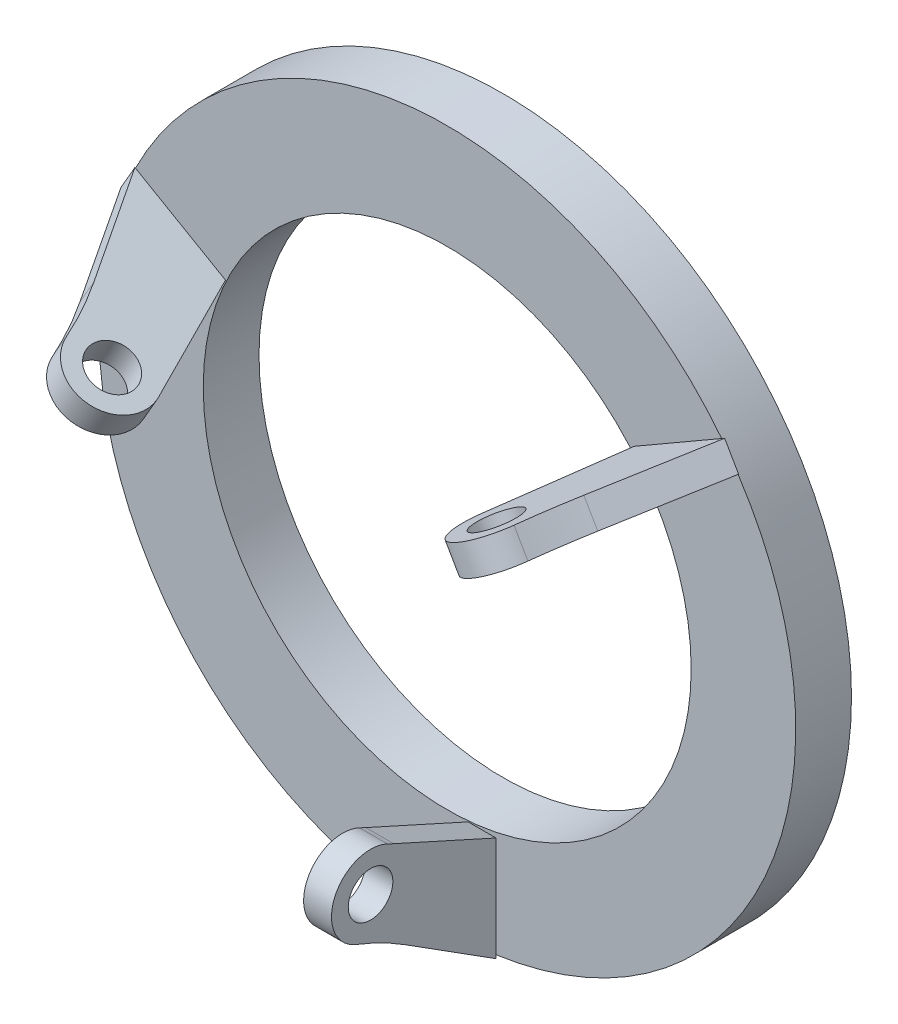
SolidWorks part; units mm, degrees
ref_plane "Piano frontale" through (0, 0, 0) normal (0, 0, 1) x (1, 0, 0)
ref_plane "Piano superiore" through (0, 0, 0) normal (0, 1, 0) x (1, 0, 0)
ref_plane "Piano destro" through (0, 0, 0) normal (1, 0, 0) x (0, 0, -1)
sketch "Schizzo1" plane through (0, 0, 0) normal (0, 0, 1) x (1, 0, 0)
  line L1 (-14.2894, 8.25) -> (-17.6966, 2.3486) construction
  line L2 (14.2894, 8.25) -> (9.3231, 16.8519) construction
  line L3 (12.8744, 5.701) -> (17.2045, 8.201) construction
  line L8 (20.1786, 13.0341) -> (11.4813, 8.0174) construction
  line L9 (11.4813, 8.0174) -> (9.5759, 11.3208) construction
  line L10 (9.5759, 11.3208) -> (18.2733, 16.3374) construction
  line L11 (18.2733, 16.3374) -> (20.1786, 13.0341) construction
  line L12 (-14.6251, 2.3486) -> (-23.5472, 7.5156) construction
  line L13 (-23.5472, 7.5156) -> (-21.5497, 10.9646) construction
  line L14 (-21.5497, 10.9646) -> (-12.6276, 5.7976) construction
  line L15 (-12.6276, 5.7976) -> (-14.6251, 2.3486) construction
  line L16 (12.1244, 7) -> (16.4545, 9.5) construction
  line L17 (0, -16.5) -> (10.6371, -16.5) construction
  line L18 (-1.5, -14) -> (-1.5, -19) construction
  line L19 (-11.3744, 8.299) -> (-15.7045, 10.799) construction
  line L20 (11.3744, 8.299) -> (15.7045, 10.799) construction
  line L21 (1.5, -14) -> (1.5, -19) construction
  line L22 (-12.1244, 7) -> (-16.4545, 9.5) construction
  line L23 (-12.8744, 5.701) -> (-17.2045, 8.201) construction
  line L24 (21.6506, 12.5) -> (32.2262, 18.6058) construction
  line L26 (0, -14) -> (0, -19) construction
  circle A0 centre (0, 0) radius 17.3182 construction
  circle A1 centre (0, 0) radius 25 construction
  circle A2 centre (0, 0) radius 14 construction
  circle A4 centre (0, 0) radius 19 construction
  point P24 (0, -27.5934)
  point P25 (-27.753, 16.0232)
  dimension "D3" = 28
  dimension "D6" = 38
  dimension "D1" = 1.5
  dimension "D2" = 1.5
sketch "Schizzo2" plane through (0, 0, 0) normal (0, 0, 1) x (1, 0, 0)
  circle A0 centre (0, 0) radius 17.5
  circle A1 centre (0, 0) radius 25
  dimension "D1" = 50
  dimension "D2" = 35
extrude "Estrusione-Estrusione1" add sketch "Schizzo2" along normal blind 4
ref_plane "Piano1" through (-0.75, 1.299, 0) normal (-0.5, 0.866, 0) x (0, 0, -1)
ref_plane "Piano2" through (-0.75, -1.299, 0) normal (-0.5, -0.866, 0) x (-0.866, 0.5, 0)
ref_plane "Piano3" through (1.5, 0, 0) normal (1, 0, 0) x (0, 0, -1)
ref_plane "Piano4" through (-14.2894, 8.25, 0) normal (-0.866, 0.5, 0) x (0, 0, 1)
ref_plane "Piano5" through (14.2894, 8.25, 0) normal (0.866, 0.5, 0) x (0, 0, -1)
ref_plane "Piano6" through (0, -16.5, 0) normal (0, -1, 0) x (-1, 0, 0)
ref_plane "Piano7" through (0, 0, 15) normal (0, 0, 1) x (1, 0, 0)
sketch "Schizzo3" plane through (-0.75, 1.299, 0) normal (-0.5, 0.866, 0) x (0, 0, -1)
  line L0 (-11.3415, -14.1842) -> (-4, -17.5)
  line L1 (-4, -25) -> (-10.5231, -20.8687)
  line L2 (-4, -17.5) -> (-4, -25)
  arc A0 (-11.7853, -13.9772) -> (-14.01, -19.1115) centre (-13, -16.5) ccw
  circle A1 centre (-13, -16.5) radius 1.6
  arc A2 (-11.3415, -14.1842) -> (-11.7853, -13.9772) centre (-3.1093, 4.043) cw
  arc A3 (-10.5231, -20.8687) -> (-14.01, -19.1115) centre (-21.2242, -37.7651) ccw
  point P14 (-13, -19.3)
  dimension "D1" = 9
  dimension "D2" = 3.2
extrude "Estrusione-Estrusione2" add sketch "Schizzo3" along normal blind 2
ref_axis "Assi1" through (0, 0, -0.2) along (0, 0, 1)
pattern_circular "RipetizioneCircolare1" count 3 every 120 about axis through (0, 0, -0.2) along (0, 0, 1) of "Estrusione-Estrusione2"
